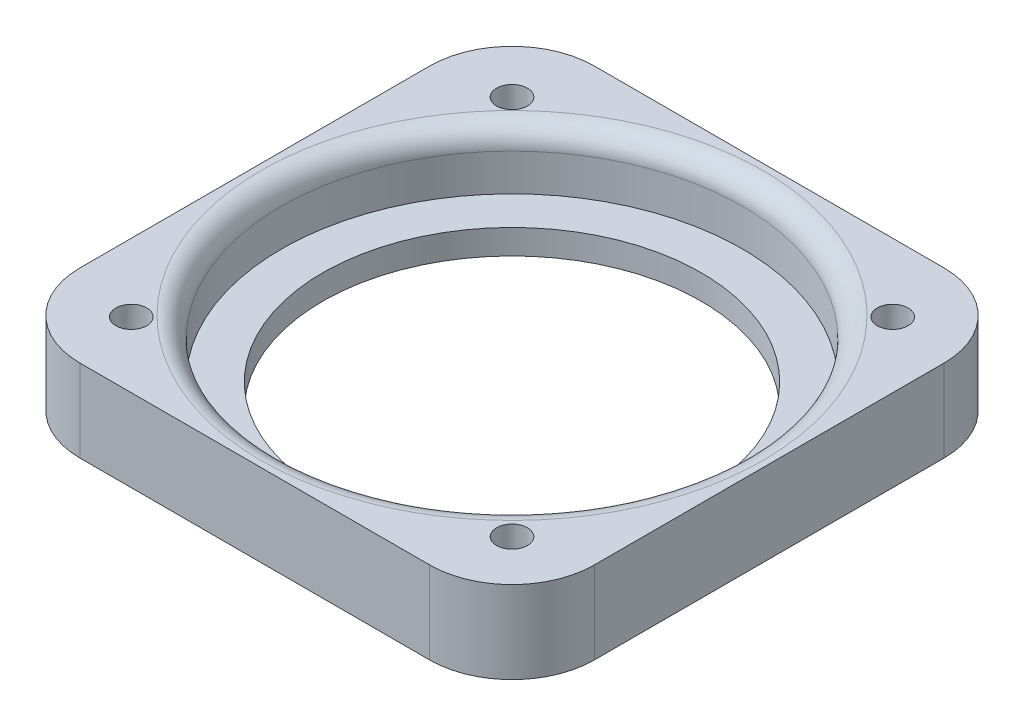
SolidWorks part; units mm, degrees
ref_plane "前视基准面" through (0, 0, 0) normal (0, 0, 1) x (1, 0, 0)
ref_plane "上视基准面" through (0, 0, 0) normal (0, 1, 0) x (1, 0, 0)
ref_plane "右视基准面" through (0, 0, 0) normal (1, 0, 0) x (0, 0, -1)
sketch "草图1" plane through (0, 0, 0) normal (0, 1, 0) x (1, 0, 0)
  circle A0 centre (0, 0) radius 25
extrude "凸台-拉伸1" add sketch "草图1" along normal blind 8
sketch "草图2" plane through (0, 8, 0) normal (0, 1, 0) x (1, 0, 0)
  circle A0 centre (0, 0) radius 22.4
  dimension "D1" = 44.8
extrude "切除-拉伸1" cut sketch "草图2" against normal blind 5.6
sketch "草图3" plane through (0, 2.4, 0) normal (0, 1, 0) x (1, 0, 0)
  circle A0 centre (0, 0) radius 18.4
  circle A1 centre (0, 0) radius 22.4 construction
  dimension "D1" = 4
extrude "切除-拉伸2" cut sketch "草图3" against normal blind 12.5
sketch "草图4" plane through (0, 0, 0) normal (0, 1, 0) x (1, 0, 0)
  line L1 (-25, 25) -> (25, 25)
  line L2 (-25, 25) -> (-25, -25)
  line L3 (-25, -25) -> (25, -25)
  line L4 (25, 25) -> (25, -25)
  line L5 (-25, 25) -> (25, -25) construction
  line L6 (-25, -25) -> (25, 25) construction
  circle A0 centre (0, 0) radius 25
  circle A1 centre (-18.3848, 18.3848) radius 1.5
  circle A2 centre (18.6152, 18.3848) radius 1.5
  circle A3 centre (18.6152, -18.6152) radius 1.5
  circle A4 centre (-18.3848, -18.6152) radius 1.5
  point P0 (0, 0)
  point P20 (0.1152, -0.1152)
  dimension "D3" = 3
  dimension "D4" = 26
  dimension "D6" = 37
  dimension "D7" = 37
  dimension "D1" = 50
  dimension "D2" = 50
  dimension "D5" = 4
extrude "凸台-拉伸2" add sketch "草图4" along normal blind 8 contours A0 L1 L2 | A0 L4 L1 | A0 L2 L3 | A0 L3 L4 region at (-19.4617, 0, -19.4617) region at (12.5, 0, -24.6464) region at (-23.5702, 0, 9.3406) region at (24.6464, 0, 12.5)
fillet "圆角1" radius 8 4 edges at (-25, 4, 25) (25, 4, 25) (25, 4, -25) (-25, 4, -25)
sketch "草图5" plane through (0, 8, 0) normal (0, 1, 0) x (1, 0, 0)
  circle A0 centre (-18.3848, 18.3848) radius 1.5
  circle A1 centre (18.6152, 18.3848) radius 1.5
  circle A2 centre (18.6152, -18.6152) radius 1.5
  circle A3 centre (-18.3848, -18.6152) radius 1.5
  point P12 (0.1152, -0.1152)
  dimension "D1" = 4
extrude "切除-拉伸3" cut sketch "草图5" against normal blind 15
fillet "圆角2" radius 2 1 edges at (0, 8, 22.4)
sketch "草图6" plane through (0, 0, 0) normal (0, -1, 0) x (1, 0, 0)
  circle A0 centre (-18.3848, 18.6152) radius 3.5
  dimension "D1" = 7
extrude "切除-拉伸4" cut sketch "草图6" against normal blind 2
pattern_circular "阵列(圆周)1" count 4 over 360 about axis through (0, 0, 0) along (0, 1, 0) of "切除-拉伸4"
